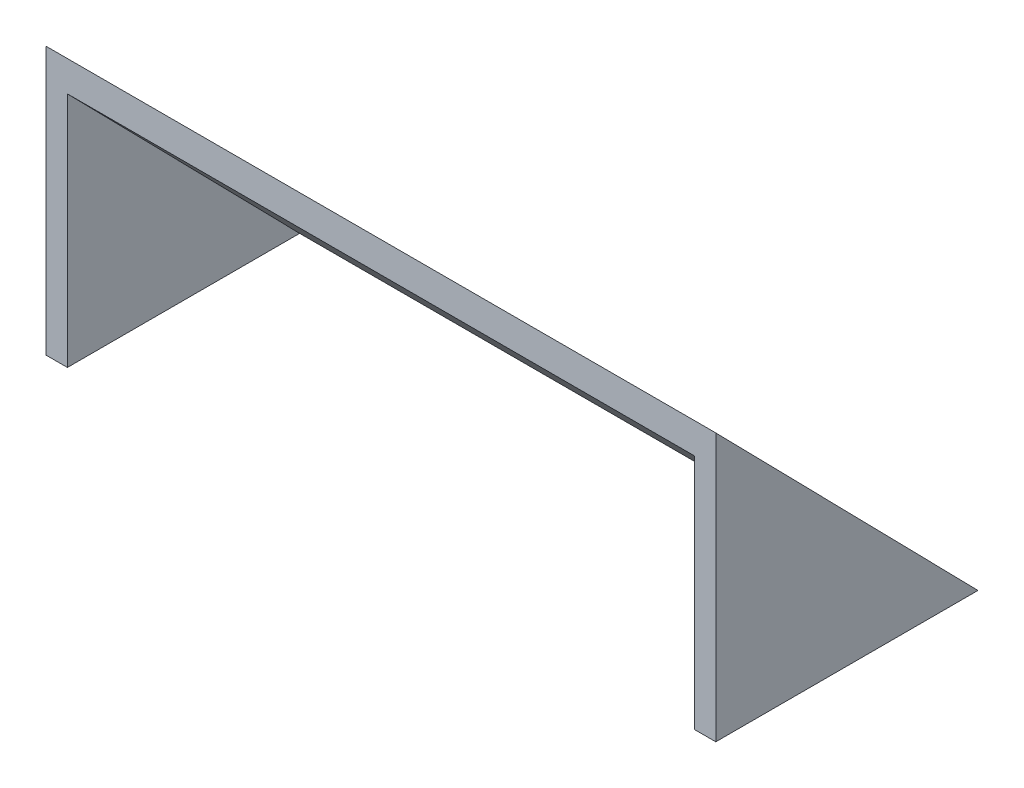
SolidWorks part; units mm, degrees
ref_plane "Přední rovina" through (0, 0, 0) normal (0, 0, 1) x (1, 0, 0)
ref_plane "Horní rovina" through (0, 0, 0) normal (0, 1, 0) x (1, 0, 0)
ref_plane "Pravá rovina" through (0, 0, 0) normal (1, 0, 0) x (0, 0, -1)
sketch "Skica1" plane through (0, 0, 0) normal (1, 0, 0) x (0, 0, -1)
  line L0 (0, 0) -> (0, 15)
  line L1 (0, 15) -> (14.7, 0)
  line L2 (14.7, 0) -> (0, 0)
  dimension "D1" = 14.7
  dimension "D2" = 15
extrude "Přidat vysunutím1" add sketch "Skica1" along normal blind 1.2
sketch "Skica2" plane through (0, 7.3485, -7.4985) normal (0, 0.6999, -0.7142) x (-1, 0, 0)
  line L1 (-1.2, 10.7132) -> (-36.35, 10.7132)
  line L2 (-1.2, 10.7132) -> (-1.2, -10.289)
  line L3 (-1.2, -10.289) -> (-36.35, -10.289)
  line L4 (-36.35, 10.7132) -> (-36.35, -10.289)
  dimension "D1" = 35.15
extrude "Přidat vysunutím2" add sketch "Skica2" against normal blind 1.2
pattern_linear "LinPole1" count 2 spacing 36.35 along (1, 0, 0) of "Přidat vysunutím1"
sketch "Skica3" plane through (37.55, 0, 0) normal (1, 0, 0) x (0, 0, -1)
  line L0 (0, 15) -> (0, 0) construction
  line L1 (0, 12.6666) -> (-1.5149, 12.6666)
  line L2 (0, 12.6666) -> (0, 17.0043)
  line L3 (0, 17.0043) -> (-1.5149, 17.0043)
  line L4 (-1.5149, 12.6666) -> (-1.5149, 17.0043)
  line L5 (0, 0) -> (14.7, 0) construction
  line L6 (12.063, 0) -> (16.5322, 0)
  line L7 (12.063, 0) -> (12.063, -2.5315)
  line L8 (12.063, -2.5315) -> (16.5322, -2.5315)
  line L9 (16.5322, 0) -> (16.5322, -2.5315)
extrude "Odebrat vysunutím1" cut sketch "Skica3" against normal through all
